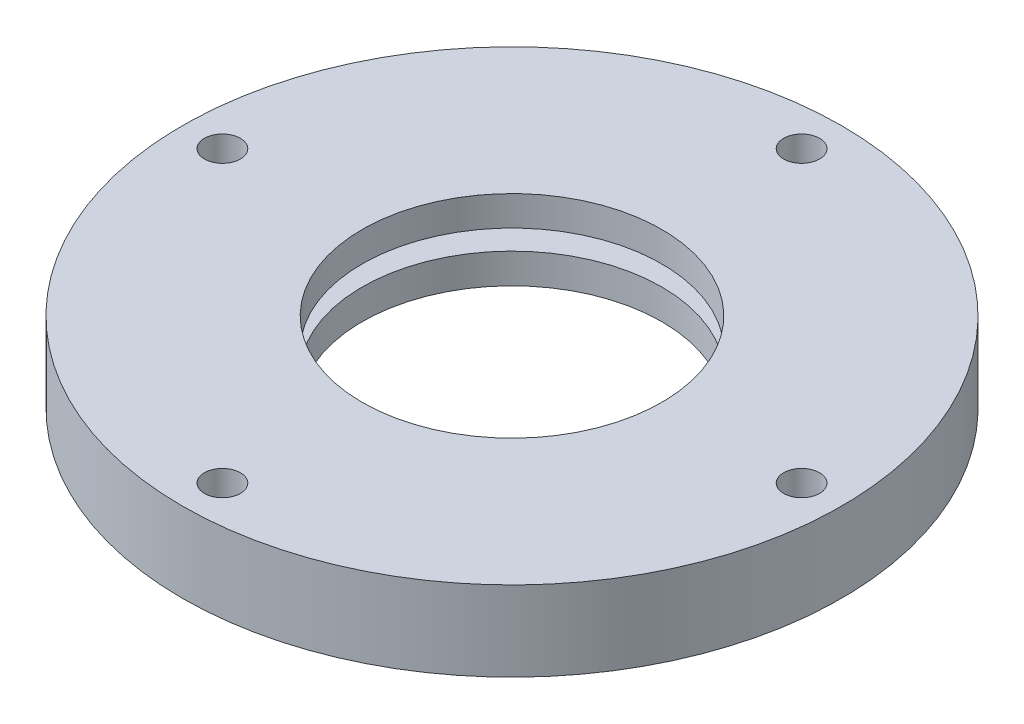
SolidWorks part; units mm, degrees
ref_plane "Front Plane" through (0, 0, 0) normal (0, 0, 1) x (1, 0, 0)
ref_plane "Top Plane" through (0, 0, 0) normal (0, 1, 0) x (1, 0, 0)
ref_plane "Right Plane" through (0, 0, 0) normal (1, 0, 0) x (0, 0, -1)
sketch "Sketch1" plane through (0, 0, 0) normal (0, 1, 0) x (1, 0, 0)
  circle A0 centre (0, 0) radius 33
  circle A1 centre (-29, 0) radius 1.5
  circle A2 centre (0, 0) radius 29 construction
  circle A3 centre (0, 29) radius 1.5
  circle A4 centre (29, 0) radius 1.5
  circle A5 centre (0, -29) radius 1.5
  point P15 (0, 0)
  dimension "D1" = 66
  dimension "D2" = 4
  dimension "D3" = 3
  dimension "D4" = 4
extrude "Boss-Extrude1" add sketch "Sketch1" along normal blind 8
hole_wizard "CSK for M3 Flat Head Machine Screw1" positions "Sketch2" profile "Sketch3" countersink size "M3" standard "ANSI Metric" end condition through all
sketch "Sketch2" plane through (0, 0, 0) normal (0, -1, 0) x (-1, 0, 0)
  point P0 (0, -29)
  point P3 (29, 0)
  point P6 (0, 29)
  point P9 (-29, 0)
sketch "Sketch3" plane through (0, 0, 29) normal (1, 0, 0) x (0, 0, -1)
  line L0 (0, 0) -> (0, 8)
  line L1 (0, 8) -> (1.8, 8)
  line L2 (1.8, 8) -> (1.8, 1.35)
  line L3 (1.8, 1.35) -> (3.15, 0)
  line L5 (3.15, 0) -> (0, 0)
  line L6 (-1.8, 1.35) -> (-3.15, 0) construction
  line L11 (0, -6.35) -> (0, 107.95) construction
  dimension "Thru Hole Dia." = 3.6
  dimension "Thru Hole Depth" = 8
  dimension "Near C'Sink Dia." = 6.3
  dimension "Near C'Sink Angle" = 90
sketch "Croquis1" plane through (0, 0, 0) normal (0, -1, 0) x (1, 0, 0)
  circle A0 centre (0, 0) radius 15
  dimension "D1" = 30
extrude "Cortar-Extruir1" cut sketch "Croquis1" against normal up to next
ref_axis "Eje1" through (0, 8, 0) along (0, -1, 0)
ref_plane "Plano1" through (-33, 0, 0) normal (-1, 0, 0) x (0, 0, 1)
sketch "Croquis2" plane through (-33, 0, 0) normal (-1, 0, 0) x (0, 0, 1)
  line L0 (0, 0) -> (0, 8.0219) construction
  line L1 (0, 8) -> (0, 0) construction
  line L3 (-20, 5.0109) -> (20, 5.0109)
  line L4 (-20, 5.0109) -> (-20, 3.0109)
  line L5 (-20, 3.0109) -> (20, 3.0109)
  line L6 (20, 5.0109) -> (20, 3.0109)
  line L7 (-20, 5.0109) -> (20, 3.0109) construction
  line L8 (-20, 3.0109) -> (20, 5.0109) construction
  point P5 (0, 4.0109)
  dimension "D1" = 40
  dimension "D2" = 2
extrude "Cortar-Extruir2" cut sketch "Croquis2" against normal blind 55
